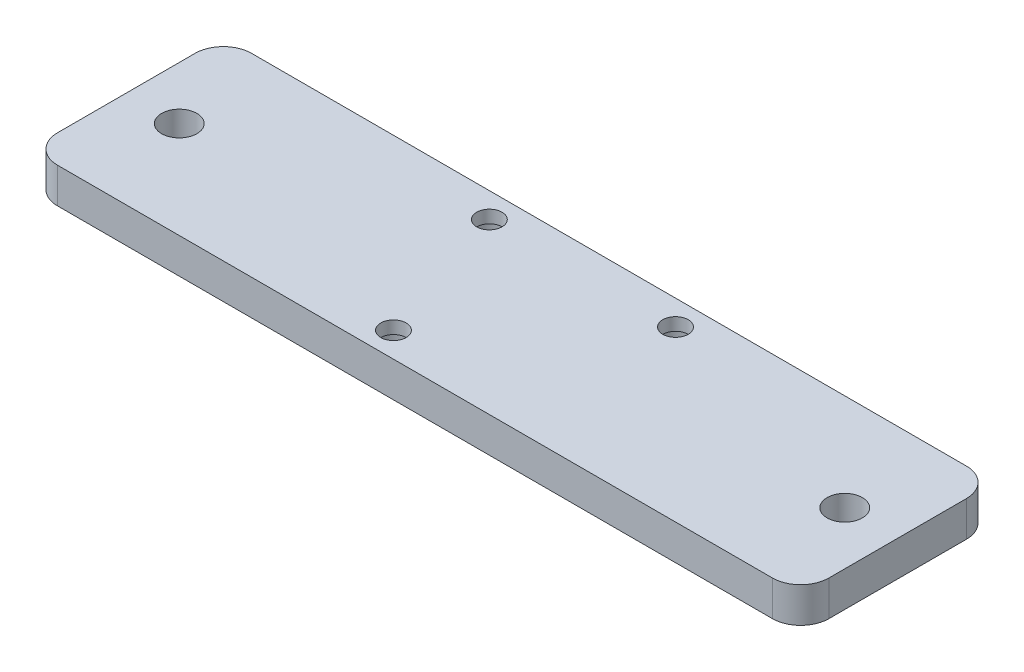
SolidWorks part; units mm, degrees
ref_plane "Front Plane" through (0, 0, 0) normal (0, 0, 1) x (1, 0, 0)
ref_plane "Top Plane" through (0, 0, 0) normal (0, 1, 0) x (1, 0, 0)
ref_plane "Right Plane" through (0, 0, 0) normal (1, 0, 0) x (0, 0, -1)
sketch "Sketch1" plane through (0, 0, 0) normal (0, 1, 0) x (1, 0, 0)
  line L0 (0, 0) -> (16.764, 0) construction
  line L1 (0, 0) -> (0, 15.9426) construction
  line L2 (16.764, 0) -> (16.764, -25.908) construction
  line L3 (16.764, -25.908) -> (-8.128, -25.908) construction
  line L4 (16.764, -12.954) -> (60.198, -12.954) construction
  line L5 (16.764, -12.954) -> (-59.6597, -12.954) construction
  line L6 (-59.6597, -12.954) -> (-69.1847, -12.954) construction
  line L7 (60.198, -12.954) -> (69.723, -12.954) construction
  line L8 (69.723, -30.4165) -> (69.723, 4.5085)
  line L9 (-69.1847, -30.4165) -> (-69.1847, 4.5085)
  line L10 (-69.1847, 4.5085) -> (69.723, 4.5085)
  line L11 (-69.1847, -30.4165) -> (69.723, -30.4165)
  circle A0 centre (16.764, 0) radius 2.286
  circle A1 centre (-16.764, 0) radius 2.286
  circle A2 centre (-8.128, -25.908) radius 2.286
  circle A3 centre (60.198, -12.954) radius 3.175
  circle A4 centre (-59.6597, -12.954) radius 3.175
extrude "Boss-Extrude1" add sketch "Sketch1" along normal blind 6.35
sketch "Sketch2" plane through (0, 0, 0) normal (0, -1, 0) x (1, 0, 0)
  circle A0 centre (-8.128, 25.908) radius 3.556
  circle A1 centre (-16.764, 0) radius 3.556
  circle A2 centre (16.764, 0) radius 3.556
extrude "Cut-Extrude1" cut sketch "Sketch2" against normal blind 4.064 contours A0 | A1 | A2
fillet "Fillet1" radius 5.08 4 edges at (69.723, 3.175, -4.5085) (69.723, 3.175, 30.4165) (-69.1847, 3.175, -4.5085) (-69.1847, 3.175, 30.4165)
ref_axis "Axis1" through (-16.764, 6.35, 0) along (0, -1, 0)
ref_axis "Axis2" through (16.764, 6.35, 0) along (0, -1, 0)
ref_axis "Axis5" through (-8.128, 6.35, 25.908) along (0, -1, 0)
ref_axis "Axis6" through (-59.6597, 6.35, 12.954) along (0, -1, 0)
ref_axis "Axis7" through (60.198, 6.35, 12.954) along (0, -1, 0)
